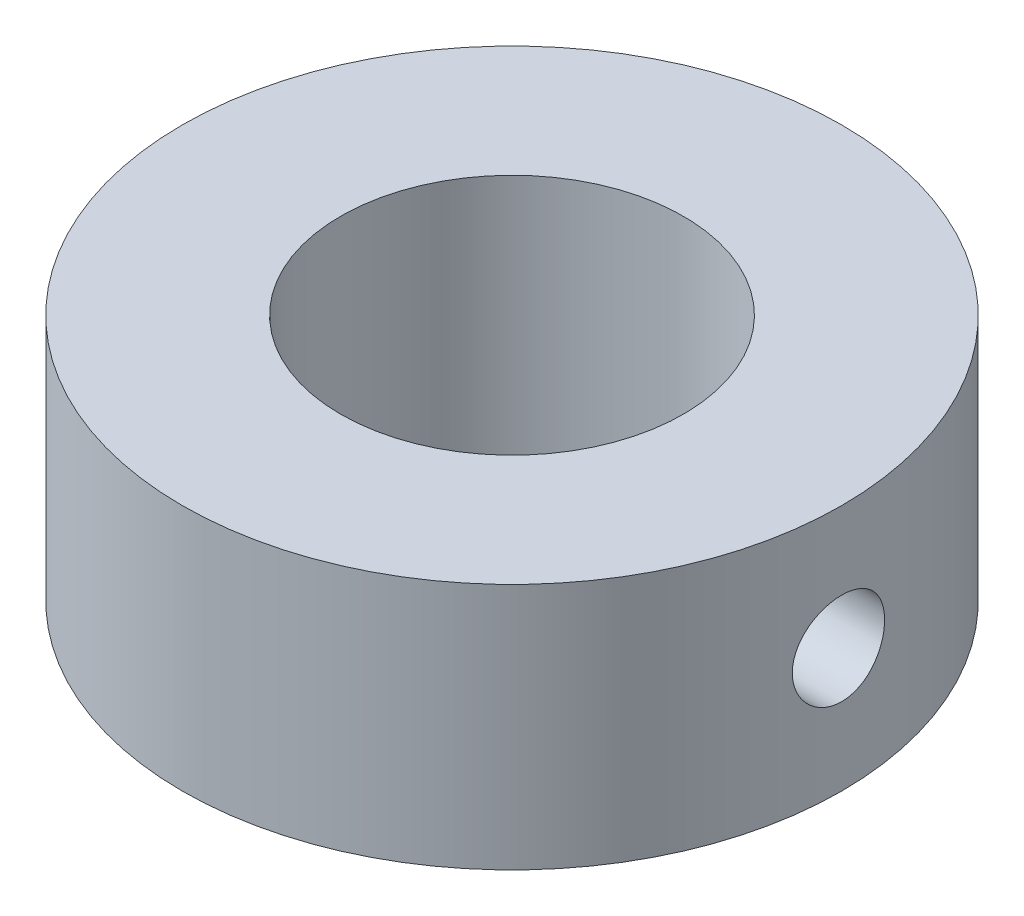
SolidWorks part; units mm, degrees
material "Polycarbonate"
ref_plane "Front Plane" through (0, 0, 0) normal (0, 0, 1) x (1, 0, 0)
ref_plane "Top Plane" through (0, 0, 0) normal (0, 1, 0) x (1, 0, 0)
ref_plane "Right Plane" through (0, 0, 0) normal (1, 0, 0) x (0, 0, -1)
sketch "Sketch1" plane through (0, 0, 0) normal (0, 1, 0) x (1, 0, 0)
  circle A0 centre (0, 0) radius 3.302
  circle A1 centre (0, 0) radius 6.35
  dimension "D1" = 6.604
  dimension "D2" = 12.7
extrude "Boss-Extrude1" add sketch "Sketch1" along normal blind 4.7625
hole_wizard "#2-64 Tapped Hole1" positions "Sketch2" profile "Sketch3" tap size "#2-64" standard "ANSI Inch" end condition through all
sketch "Sketch2" plane through (0, 0, 0) normal (1, 0, 0) x (0, 0, -1)
  line L0 (6.35, 4.7625) -> (-6.35, 4.7625) construction
  line L1 (-6.35, 0) -> (6.35, 0) construction
  line L2 (6.35, 4.7625) -> (-6.35, 4.7625) construction
  line L3 (-6.35, 0) -> (6.35, 0) construction
  line L4 (0, 4.7625) -> (0, 0) construction
  point P0 (0, 2.3813)
sketch "Sketch3" plane through (0, 2.3813, 0) normal (0, 1, 0) x (0, 0, 1)
  line L0 (0, 0) -> (0, 6.35)
  line L1 (0, 6.35) -> (0.889, 6.35)
  line L2 (0.889, 6.35) -> (0.889, 0)
  line L5 (0.889, 0) -> (0, 0)
  line L11 (0, -6.35) -> (0, 107.95) construction
  dimension "Thru Tap Drill Dia." = 1.778
  dimension "Thru Tap Drill Depth" = 6.35
cosmetic thread "Hole Thread1" parameters "D2"=2.1844
